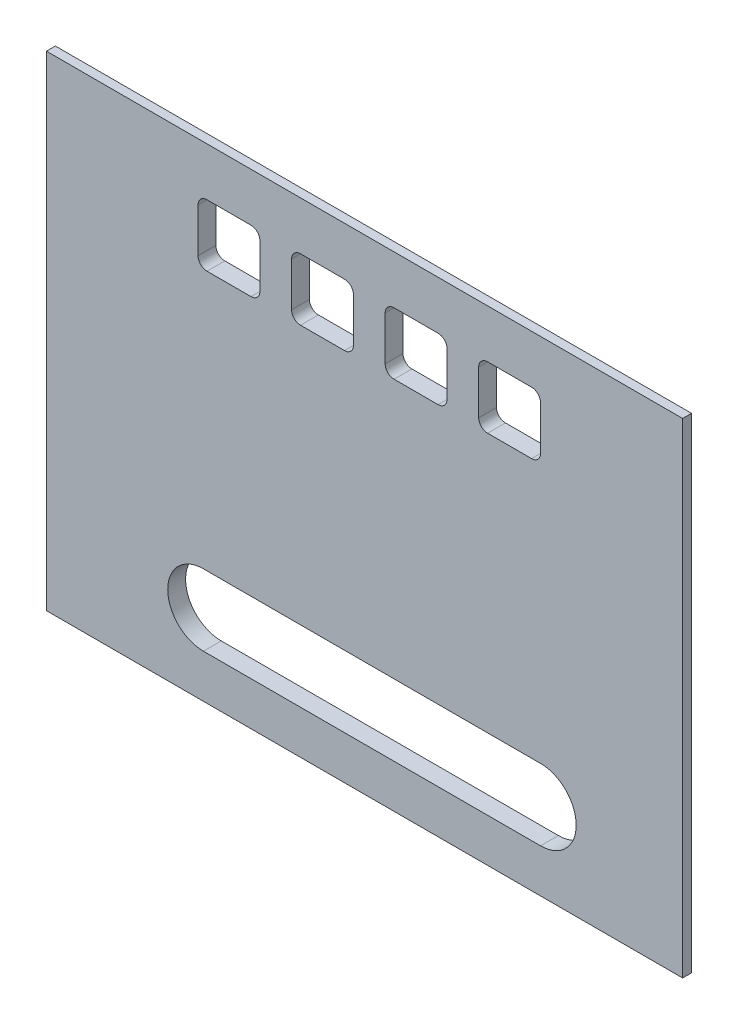
SolidWorks part; units mm, degrees
ref_plane "Спереди" through (0, 0, 0) normal (0, 0, 1) x (1, 0, 0)
ref_plane "Сверху" through (0, 0, 0) normal (0, 1, 0) x (1, 0, 0)
ref_plane "Справа" through (0, 0, 0) normal (1, 0, 0) x (0, 0, -1)
other "Configuration Table"
sketch "Эскиз1" plane through (0, 0, 0) normal (0, 0, 1) x (1, 0, 0)
  line L1 (3, 3) -> (104, 3)
  line L2 (3, 3) -> (3, 77)
  line L3 (3, 77) -> (104, 77)
  line L4 (104, 3) -> (104, 77)
extrude "Бобышка-Вытянуть1" add sketch "Эскиз1" along normal blind 3
sketch "Эскиз2" plane through (0, 0, 0) normal (0, 0, 1) x (1, 0, 0)
  line L1 (0, 0) -> (107, 0)
  line L2 (0, 0) -> (0, 80)
  line L3 (0, 80) -> (107, 80)
  line L4 (107, 0) -> (107, 80)
extrude "Бобышка-Вытянуть2" add sketch "Эскиз2" along normal blind 1.5 from offset 1.5
sketch "Эскиз3" plane through (0, 0, 3) normal (0, 0, 1) x (1, 0, 0)
  line L0 (26.4, 13.3) -> (83.1, 13.3) construction
  line L1 (25.5, 62.95) -> (35.9, 62.95)
  line L2 (25.5, 62.95) -> (25.5, 73.35)
  line L3 (25.5, 73.35) -> (35.9, 73.35)
  line L4 (35.9, 62.95) -> (35.9, 73.35)
  line L5 (41.233, 62.95) -> (51.633, 62.95)
  line L6 (41.233, 62.95) -> (41.233, 73.35)
  line L7 (41.233, 73.35) -> (51.633, 73.35)
  line L8 (51.633, 62.95) -> (51.633, 73.35)
  line L9 (56.967, 62.95) -> (67.367, 62.95)
  line L10 (56.967, 62.95) -> (56.967, 73.35)
  line L11 (56.967, 73.35) -> (67.367, 73.35)
  line L12 (67.367, 62.95) -> (67.367, 73.35)
  line L13 (72.7, 62.95) -> (83.1, 62.95)
  line L14 (72.7, 62.95) -> (72.7, 73.35)
  line L15 (72.7, 73.35) -> (83.1, 73.35)
  line L16 (83.1, 62.95) -> (83.1, 73.35)
  line L17 (26.4, 19.3) -> (83.1, 19.3)
  line L18 (26.4, 7.3) -> (83.1, 7.3)
  arc A0 (26.4, 19.3) -> (26.4, 7.3) centre (26.4, 13.3) ccw
  arc A1 (83.1, 7.3) -> (83.1, 19.3) centre (83.1, 13.3) ccw
  point P18 (54.75, 13.3)
extrude "Вырез-Вытянуть1" cut sketch "Эскиз3" against normal blind 5
sketch "Эскиз4" plane through (0, 0, 0) normal (0, 0, 1) x (1, 0, 0)
  line L1 (3, 77) -> (104, 77)
  line L2 (3, 77) -> (3, 78.5)
  line L3 (3, 78.5) -> (104, 78.5)
  line L4 (104, 77) -> (104, 78.5)
extrude "top_rear_inner_extension_1p5mm" add sketch "Эскиз4" along normal blind 3
sketch "Эскиз5" plane through (0, 0, 0) normal (0, 0, 1) x (1, 0, 0)
  line L1 (0, 80) -> (107, 80)
  line L2 (0, 80) -> (0, 81.5)
  line L3 (0, 81.5) -> (107, 81.5)
  line L4 (107, 80) -> (107, 81.5)
extrude "top_rear_outer_skin_extension_1p5mm" add sketch "Эскиз5" along normal blind 1.5 from offset 1.5
fillet "tool_D3_R1p5_button_corners" radius 1.5 16 edges at (72.7, 73.35, 1.5) (83.1, 73.35, 1.5) (83.1, 62.95, 1.5) (72.7, 62.95, 1.5) (56.967, 73.35, 1.5) (67.367, 73.35, 1.5) (67.367, 62.95, 1.5) (56.967, 62.95, 1.5) (41.233, 73.35, 1.5) (51.633, 73.35, 1.5) (51.633, 62.95, 1.5) (41.233, 62.95, 1.5) (25.5, 62.95, 1.5) (35.9, 62.95, 1.5) (35.9, 73.35, 1.5) (25.5, 73.35, 1.5) tangent propagation no
